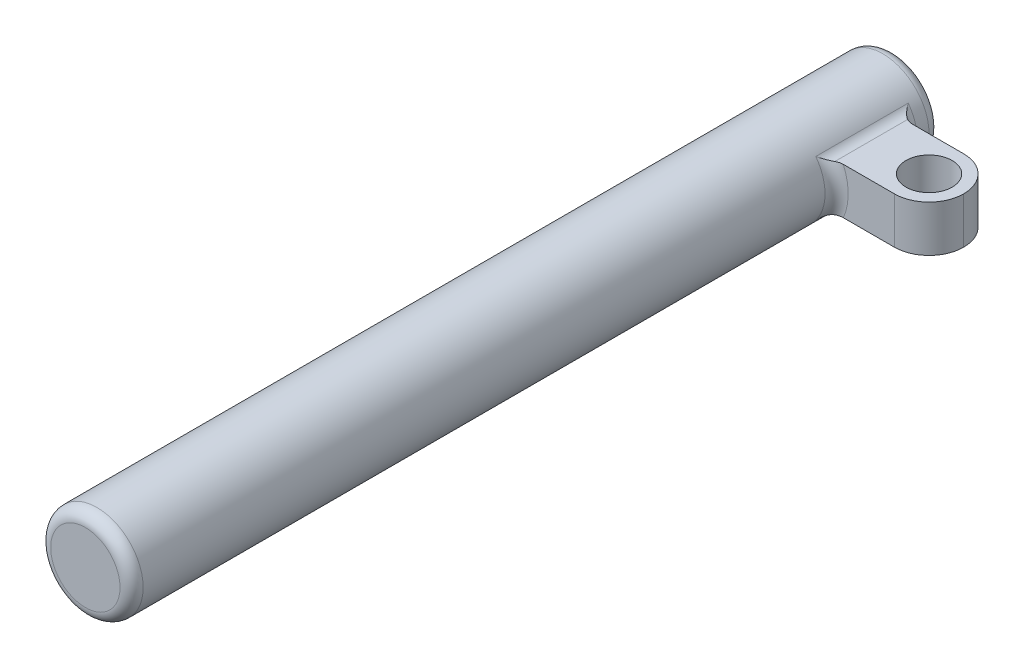
SolidWorks part; units mm, degrees
ref_plane "Front Plane" through (0, 0, 0) normal (0, 0, 1) x (1, 0, 0)
ref_plane "Top Plane" through (0, 0, 0) normal (0, 1, 0) x (1, 0, 0)
ref_plane "Right Plane" through (0, 0, 0) normal (1, 0, 0) x (0, 0, -1)
sketch "Sketch1" plane through (0, 0, 0) normal (0, 0, 1) x (1, 0, 0)
  circle A0 centre (0, 0) radius 10.16
  dimension "D1" = 20.32
extrude "Boss-Extrude1" add sketch "Sketch1" along normal mid plane 177.8
fillet "Fillet1" radius 2.54 2 edges at (10.16, 0, -88.9) (10.16, 0, 88.9)
sketch "Sketch3" plane through (0, 0, 0) normal (1, 0, 0) x (0, 0, -1)
  line L1 (66.04, 5.08) -> (81.28, 5.08)
  line L2 (66.04, 5.08) -> (66.04, -5.08)
  line L3 (66.04, -5.08) -> (81.28, -5.08)
  line L4 (81.28, 5.08) -> (81.28, -5.08)
  line L5 (66.04, 5.08) -> (81.28, -5.08) construction
  line L6 (66.04, -5.08) -> (81.28, 5.08) construction
  point P0 (73.66, 0)
  dimension "D1" = 10.16
  dimension "D2" = 15.24
  dimension "D3" = 73.66
extrude "Boss-Extrude2" add sketch "Sketch3" along normal blind 30.48
fillet "Fillet2" radius 7.62 2 edges at (30.48, 0, -81.28) (30.48, 0, -66.04)
sketch "Sketch4" plane through (0, 5.08, 0) normal (0, 1, 0) x (1, 0, 0)
  circle A0 centre (22.86, 73.66) radius 5.08
  arc A1 (22.86, 66.04) -> (30.48, 73.66) centre (22.86, 73.66) ccw construction
  dimension "D1" = 10.16
extrude "Cut-Extrude1" cut sketch "Sketch4" against normal up to next
fillet "Fillet3" radius 2.54 4 edges at (10.16, 0, -66.04) (10.16, 0, -81.28) (8.7988, -5.08, -73.66) (8.7988, 5.08, -73.66)
